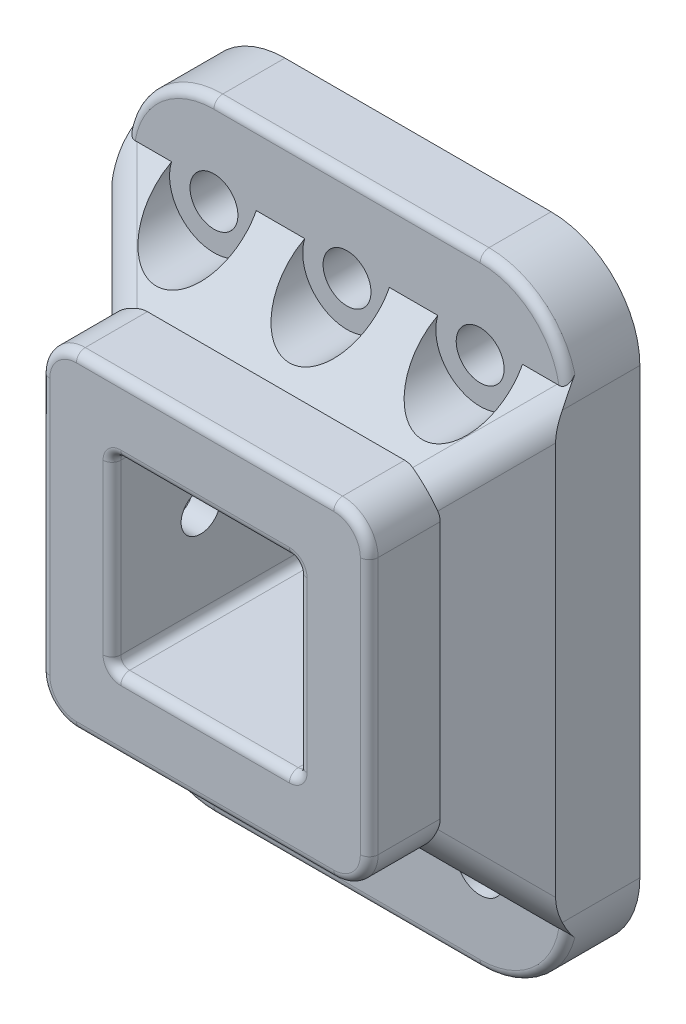
SolidWorks part; units mm, degrees
ref_plane "Plan de face" through (0, 0, 0) normal (0, 0, 1) x (1, 0, 0)
ref_plane "Plan de dessus" through (0, 0, 0) normal (0, 1, 0) x (1, 0, 0)
ref_plane "Plan de droite" through (0, 0, 0) normal (1, 0, 0) x (0, 0, -1)
sketch "Esquisse1" plane through (0, 0, 0) normal (0, 0, 1) x (1, 0, 0)
  line L0 (0, 25) -> (0, -25) construction
  line L1 (10.5, 10.5) -> (-10.5, 10.5)
  line L2 (10.5, 10.5) -> (10.5, -10.5)
  line L3 (10.5, -10.5) -> (-10.5, -10.5)
  line L4 (-10.5, 10.5) -> (-10.5, -10.5)
  line L5 (10.5, 10.5) -> (-10.5, -10.5) construction
  line L6 (10.5, -10.5) -> (-10.5, 10.5) construction
  line L7 (0, -25) -> (15, -25) construction
  line L8 (0, 0) -> (48.322, 0) construction
  line L9 (0, 25) -> (15, 25) construction
  line L11 (25, 35) -> (-25, 35)
  line L12 (25, 35) -> (25, -35)
  line L13 (25, -35) -> (-25, -35)
  line L14 (-25, 35) -> (-25, -35)
  line L15 (25, 35) -> (-25, -35) construction
  line L16 (25, -35) -> (-25, 35) construction
  circle A0 centre (15, -25) radius 2.7
  circle A1 centre (0, -25) radius 2.7
  circle A2 centre (-15, -25) radius 2.7
  circle A3 centre (-15, 25) radius 2.7
  circle A4 centre (0, 25) radius 2.7
  circle A5 centre (15, 25) radius 2.7
  point P0 (0, 0)
  dimension "D2" = 5.4
  dimension "D1" = 21
  dimension "D3" = 50
  dimension "D4" = 30
  dimension "D5" = 50
  dimension "D6" = 70
extrude "Boss.-Extru.1" add sketch "Esquisse1" along normal blind 8
sketch "Esquisse2" plane through (0, 0, 8) normal (0, 0, 1) x (1, 0, 0)
  line L1 (18.5, 18.5) -> (-18.5, 18.5)
  line L2 (18.5, 18.5) -> (18.5, -18.5)
  line L3 (18.5, -18.5) -> (-18.5, -18.5)
  line L4 (-18.5, 18.5) -> (-18.5, -18.5)
  line L5 (18.5, 18.5) -> (-18.5, -18.5) construction
  line L6 (18.5, -18.5) -> (-18.5, 18.5) construction
  line L7 (10.5, -10.5) -> (-10.5, -10.5)
  line L8 (10.5, -10.5) -> (10.5, 10.5)
  line L9 (10.5, 10.5) -> (-10.5, 10.5)
  line L10 (-10.5, -10.5) -> (-10.5, 10.5)
  line L11 (10.5, -10.5) -> (-10.5, 10.5) construction
  line L12 (10.5, 10.5) -> (-10.5, -10.5) construction
  point P0 (0, 0)
  point P6 (0, 0)
  dimension "D1" = 8
  dimension "D2" = 8
extrude "Boss.-Extru.2" add sketch "Esquisse2" along normal blind 16
fillet "Congé1" radius 10 4 edges at (25, 35, 4) (25, -35, 4) (-25, -35, 4) (-25, 35, 4)
chamfer "Chanfrein1" distance 8 angle 45 4 edges at (18.5, 0, 8) (0, -18.5, 8) (0, 18.5, 8) (-18.5, 0, 8)
fillet "Congé2" radius 4 8 edges at (21.75, -21.75, 12.75) (21.75, 21.75, 12.75) (-21.75, 21.75, 12.75) (-21.75, -21.75, 12.75) (-18.5, -18.5, 20) (-18.5, 18.5, 20) (18.5, 18.5, 20) (18.5, -18.5, 20)
fillet "Congé3" radius 1 4 edges at (10.5, 10.5, 12) (-10.5, 10.5, 12) (-10.5, -10.5, 12) (10.5, -10.5, 12)
sketch "Esquisse3" plane through (-18.5, 0, 0) normal (-1, 0, 0) x (0, 0, 1)
  line L0 (24, 0) -> (0, 0) construction
  line L1 (24, 14.5) -> (24, -14.5) construction
  circle A0 centre (14, 0) radius 2.2
  dimension "D1" = 4.4
  dimension "D2" = 10
extrude "Enlèv. mat.-Extru.1" cut sketch "Esquisse3" against normal blind 10
sketch "Esquisse4" plane through (-18.5, 0, 0) normal (-1, 0, 0) x (0, 0, 1)
  circle A0 centre (14, 0) radius 3.5
  dimension "D1" = 7
extrude "Enlèv. mat.-Extru.2" cut sketch "Esquisse4" along normal blind 10
fillet "Congé4" radius 1 8 edges at (10.2071, 10.2071, 24) (10.5, 0, 24) (10.2071, -10.2071, 24) (0, -10.5, 24) (-10.2071, -10.2071, 24) (-10.5, 0, 24) (-10.2071, 10.2071, 24) (0, 10.5, 24)
fillet "Congé5" radius 1 8 edges at (-10.2071, 10.2071, 0) (0, 10.5, 0) (10.2071, 10.2071, 0) (10.5, 0, 0) (10.2071, -10.2071, 0) (0, -10.5, 0) (-10.2071, -10.2071, 0) (-10.5, 0, 0)
fillet "Congé6" radius 1 14 edges at (-17.3284, -17.3284, 24) (-18.5, 0, 24) (-17.3284, 17.3284, 24) (0, 18.5, 24) (17.3284, 17.3284, 24) (18.5, 0, 24) (17.3284, -17.3284, 24) (-21.6035, -32.5095, 8) (21.6035, -32.5095, 8) (21.6035, 32.5095, 8) (-21.6035, 32.5095, 8) (0, -18.5, 24) (0, -35, 8) (0, 35, 8)
sketch "Esquisse5" plane through (0, 0, 8) normal (0, 0, 1) x (1, 0, 0)
  circle A0 centre (0, -25) radius 5
  circle A1 centre (15, -25) radius 5
  circle A2 centre (-15, -25) radius 5
  circle A3 centre (-15, 25) radius 5
  circle A4 centre (0, 25) radius 5
  circle A5 centre (15, 25) radius 5
  dimension "D1" = 10
extrude "Enlèv. mat.-Extru.3" cut sketch "Esquisse5" along normal blind 10
sketch "Esquisse6" plane through (-18.5, 0, 0) normal (-1, 0, 0) x (0, 0, 1)
  circle A0 centre (14, 0) radius 3.5
extrude "Enlèv. mat.-Extru.4" cut sketch "Esquisse6" against normal blind 5
